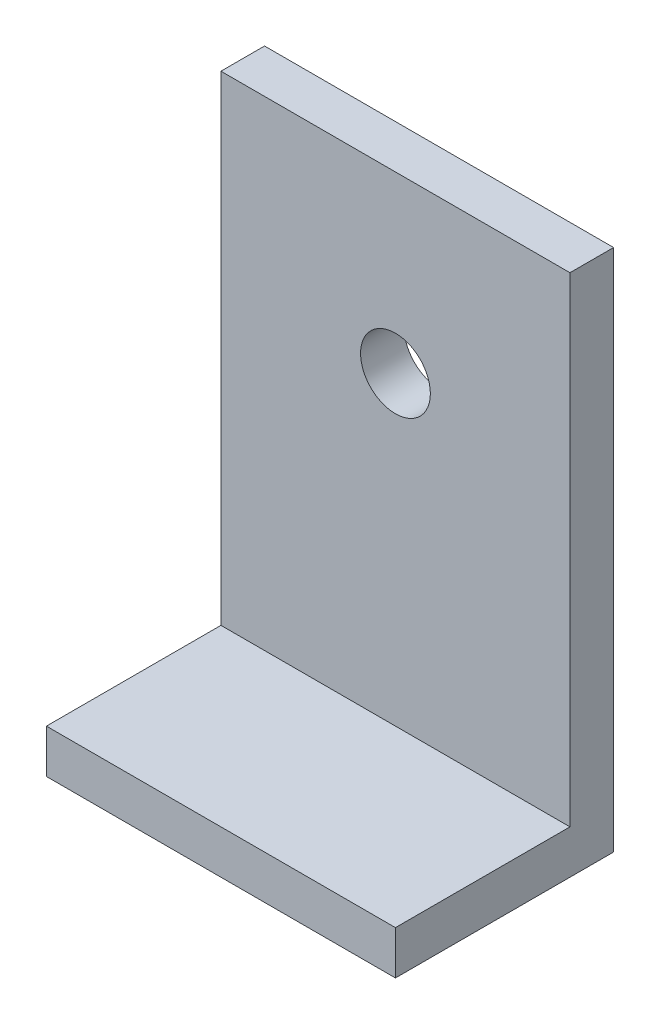
SolidWorks part; units mm, degrees
ref_plane "Front Plane" through (0, 0, 0) normal (0, 0, 1) x (1, 0, 0)
ref_plane "Top Plane" through (0, 0, 0) normal (0, 1, 0) x (1, 0, 0)
ref_plane "Right Plane" through (0, 0, 0) normal (1, 0, 0) x (0, 0, -1)
sketch "Sketch1" plane through (0, 0, 0) normal (0, 0, 1) x (1, 0, 0)
  line L0 (0, 0) -> (0, 55)
  line L1 (0, 55) -> (40, 55)
  line L2 (40, 55) -> (40, 0)
  line L3 (40, 0) -> (0, 0)
  line L4 (0, 0) -> (0, -5)
  line L5 (0, -5) -> (40, -5)
  line L6 (40, -5) -> (40, 0)
  point P7 (20, 0)
  dimension "D1" = 40
  dimension "D2" = 60
  dimension "D3" = 5
extrude "Boss-Extrude1" add sketch "Sketch1" along normal blind 5 contours L3 L2 L1 L0 region at (20, 27.5, 0)
extrude "Boss-Extrude2" add sketch "Sketch1<3>" along normal blind 25 contours L5 L6 L3 L4 region at (20, -2.5, 0)
sketch "Sketch1<3>" plane through (0, 0, 0) normal (0, 0, 1) x (1, 0, 0) same geometry as "Sketch1"
sketch "Sketch2" plane through (0, 0, 5) normal (0, 0, 1) x (1, 0, 0)
  line L2 (40, 0) -> (0, 0) construction
  line L3 (0, 0) -> (0, 55) construction
  circle A0 centre (20, 35) radius 4
  dimension "D1" = 8
  dimension "D2" = 35
  dimension "D3" = 20
extrude "Cut-Extrude1" cut sketch "Sketch2" against normal through all
